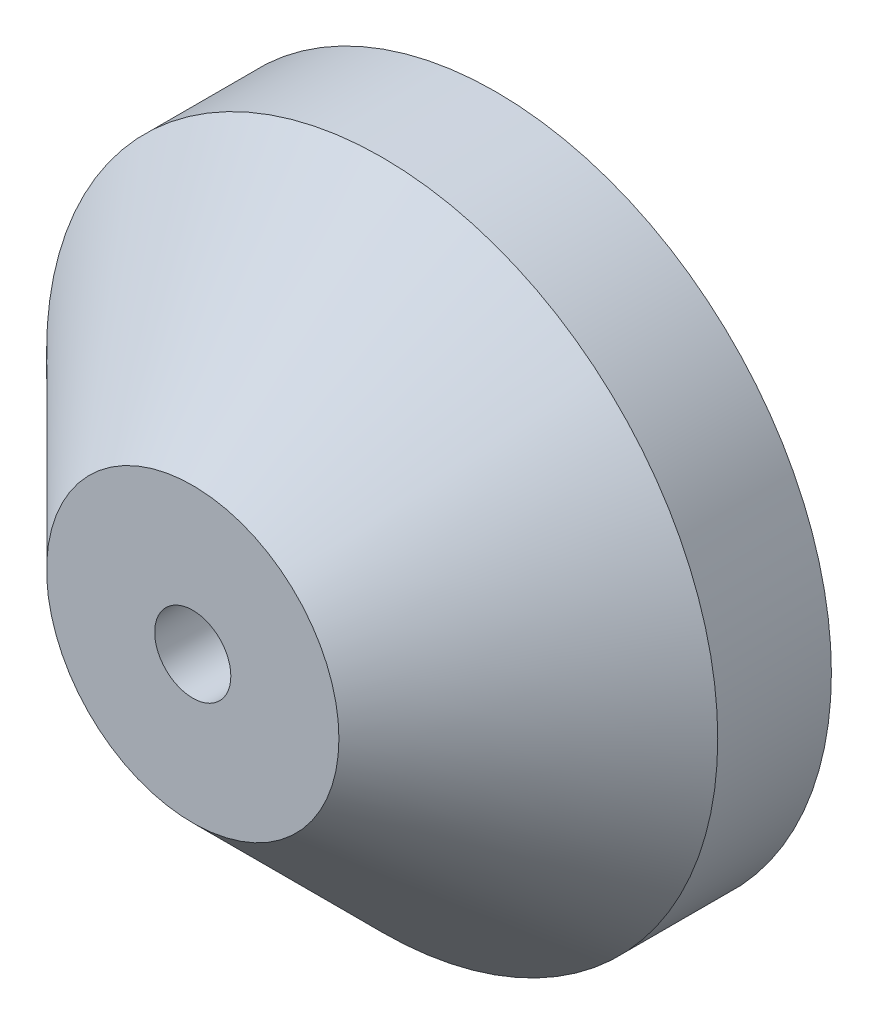
SolidWorks part; units mm, degrees
material "ABS"
ref_plane "Front Plane" through (0, 0, 0) normal (0, 0, 1) x (1, 0, 0)
ref_plane "Top Plane" through (0, 0, 0) normal (0, 1, 0) x (1, 0, 0)
ref_plane "Right Plane" through (0, 0, 0) normal (1, 0, 0) x (0, 0, -1)
sketch "Sketch1" plane through (0, 0, 0) normal (0, 0, 1) x (1, 0, 0)
  circle A0 centre (0, 0) radius 22.5
  dimension "D1" = 45
extrude "Boss-Extrude1" add sketch "Sketch1" against normal blind 20.32
sketch "Sketch2" plane through (0, 0, -20.32) normal (0, 0, -1) x (-1, 0, 0)
  circle A0 centre (0, 0) radius 17.5
  dimension "D1" = 35
extrude "Cut-Extrude1" cut sketch "Sketch2" against normal blind 11
sketch "Sketch5" plane through (0, 0, 0) normal (0, 0, 1) x (1, 0, 0)
  point P0 (0, 0)
hole_wizard "1/4-20 Tapped Hole1" positions "Sketch7" profile "Sketch8" tap size "1/4-20" standard "ANSI Inch" end condition up to next
sketch "Sketch7" plane through (0, 0, 0) normal (0, 0, 1) x (1, 0, 0)
  point P0 (0, 0)
sketch "Sketch8" plane through (0, 0, 0) normal (1, 0, 0) x (0, -1, 0)
  line L0 (0, 0) -> (0, 9.32)
  line L1 (0, 9.32) -> (2.5527, 9.32)
  line L2 (2.5527, 9.32) -> (2.5527, 0)
  line L5 (2.5527, 0) -> (0, 0)
  line L11 (0, -6.35) -> (0, 107.95) construction
  dimension "Thru Tap Drill Dia." = 5.1054
  dimension "Thru Tap Drill Depth" = 9.32
cosmetic thread "Hole Thread1" parameters "D2"=6.35
chamfer "Chamfer1" distance 12.7 angle 45 1 edges at (22.5, 0, 0)
